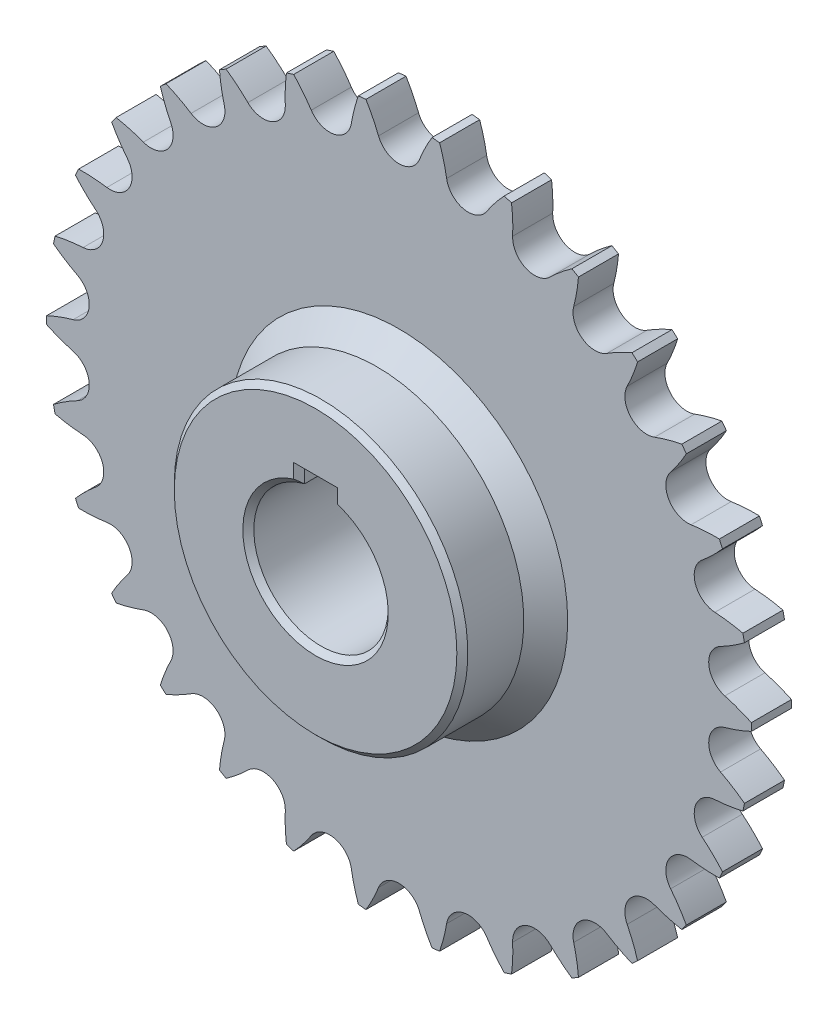
SolidWorks part; units mm, degrees
ref_plane "Front" through (0, 0, 0) normal (0, 0, 1) x (1, 0, 0)
ref_plane "Top" through (0, 0, 0) normal (0, 1, 0) x (1, 0, 0)
ref_plane "Right" through (0, 0, 0) normal (1, 0, 0) x (0, 0, -1)
sketch "Sketch1" plane through (0, 0, 0) normal (0, 0, 1) x (1, 0, 0)
  line L4 (0, -131.4524) -> (0, 131.4524) construction
  line L5 (-131.4524, 0) -> (131.4524, 0) construction
  line L6 (-1.75, -1.75) -> (1.75, 1.75)
  line L7 (-1.75, 1.75) -> (1.75, -1.75)
  circle A174 centre (0, 0) radius 113.558 construction
  circle A175 centre (0, 0) radius 121.498 construction
  arc A176 (117.2084, 19.8216) -> (118.7683, 4.9806) centre (120.9114, 12.7083) ccw
  arc A177 (128.4449, 1.3906) -> (118.7683, 4.9806) centre (102.4723, -53.7809) ccw
  arc A178 (125.9272, 25.345) -> (125.349, 28.0654) centre (0, 0) ccw
  arc A179 (117.2084, 19.8216) -> (125.9272, 25.345) centre (89.0514, 73.9108) ccw
  arc A180 (110.526, 43.7575) -> (115.1374, 29.565) centre (115.627, 37.5695) ccw
  arc A181 (125.349, 28.0654) -> (115.1374, 29.565) centre (111.4147, -31.3004) ccw
  arc A182 (117.9059, 50.9729) -> (116.7747, 53.5136) centre (0, 0) ccw
  arc A183 (110.526, 43.7575) -> (117.9059, 50.9729) centre (71.7385, 90.8105) ccw
  arc A184 (99.0131, 65.7809) -> (106.4745, 52.8574) centre (105.2891, 60.7887) ccw
  arc A185 (116.7747, 53.5136) -> (106.4745, 52.8574) centre (115.4878, -7.452) ccw
  arc A186 (104.7315, 74.373) -> (103.0967, 76.623) centre (0, 0) ccw
  arc A187 (99.0131, 65.7809) -> (104.7315, 74.373) centre (51.2903, 103.7413) ccw
  arc A188 (83.1728, 84.9294) -> (93.1581, 73.8396) centre (90.3496, 81.3512) ccw
  arc A189 (103.0967, 76.623) -> (93.1581, 73.8396) centre (114.5134, 16.7221) ccw
  arc A190 (86.9798, 94.5227) -> (84.913, 96.3836) centre (0, 0) ccw
  arc A191 (83.1728, 84.9294) -> (86.9798, 94.5227) centre (28.6004, 112.1382) ccw
  arc A192 (63.6974, 100.3661) -> (75.7702, 91.5947) centre (71.4614, 98.3582) ccw
  arc A193 (84.913, 96.3836) -> (75.7702, 91.5947) centre (108.5343, 40.1654) ccw
  arc A194 (65.4267, 110.5413) -> (63.0182, 111.9318) centre (0, 0) ccw
  arc A195 (63.6974, 100.3661) -> (65.4267, 110.5413) centre (4.6606, 115.6341) ccw
  arc A196 (41.4382, 111.4163) -> (55.0709, 105.3466) centre (49.45, 111.0665) ccw
  arc A197 (63.0182, 111.9318) -> (55.0709, 105.3466) centre (97.8117, 61.8532) ccw
  arc A198 (41.0142, 121.7286) -> (38.3691, 122.5881) centre (0, 0) ccw
  arc A199 (41.4382, 111.4163) -> (41.0142, 121.7286) centre (-19.4829, 114.0762) ccw
  arc A200 (17.3679, 117.5971) -> (31.9646, 114.4944) centre (25.2774, 118.9206) ccw
  arc A201 (38.3691, 122.5881) -> (31.9646, 114.4944) centre (82.8143, 80.8378) ccw
  arc A202 (14.8091, 127.5959) -> (12.0432, 127.8866) centre (0, 0) ccw
  arc A203 (17.3679, 117.5971) -> (14.8091, 127.5959) centre (-42.775, 107.5326) ccw
  arc A204 (-7.4614, 118.6383) -> (7.4614, 118.6383) centre (0, 121.5774) ccw
  arc A205 (12.0432, 127.8866) -> (7.4614, 118.6383) centre (64.1975, 96.2893) ccw
  arc A206 (-12.0432, 127.8866) -> (-14.8091, 127.5959) centre (0, 0) ccw
  arc A207 (-7.4614, 118.6383) -> (-12.0432, 127.8866) centre (-64.1975, 96.2893) ccw
  arc A208 (-31.9646, 114.4944) -> (-17.3679, 117.5971) centre (-25.2774, 118.9206) ccw
  arc A209 (-14.8091, 127.5959) -> (-17.3679, 117.5971) centre (42.775, 107.5326) ccw
  arc A210 (-38.3691, 122.5881) -> (-41.0142, 121.7286) centre (0, 0) ccw
  arc A211 (-31.9646, 114.4944) -> (-38.3691, 122.5881) centre (-82.8143, 80.8378) ccw
  arc A212 (-55.0709, 105.3466) -> (-41.4382, 111.4163) centre (-49.45, 111.0665) ccw
  arc A213 (-41.0142, 121.7286) -> (-41.4382, 111.4163) centre (19.4829, 114.0762) ccw
  arc A214 (-63.0182, 111.9318) -> (-65.4267, 110.5413) centre (0, 0) ccw
  arc A215 (-55.0709, 105.3466) -> (-63.0182, 111.9318) centre (-97.8117, 61.8532) ccw
  arc A216 (-75.7702, 91.5947) -> (-63.6974, 100.3661) centre (-71.4614, 98.3582) ccw
  arc A217 (-65.4267, 110.5413) -> (-63.6974, 100.3661) centre (-4.6606, 115.6341) ccw
  arc A218 (-84.913, 96.3836) -> (-86.9798, 94.5227) centre (0, 0) ccw
  arc A219 (-75.7702, 91.5947) -> (-84.913, 96.3836) centre (-108.5343, 40.1654) ccw
  arc A220 (-93.1581, 73.8396) -> (-83.1728, 84.9294) centre (-90.3496, 81.3512) ccw
  arc A221 (-86.9798, 94.5227) -> (-83.1728, 84.9294) centre (-28.6004, 112.1382) ccw
  arc A222 (-103.0967, 76.623) -> (-104.7315, 74.373) centre (0, 0) ccw
  arc A223 (-93.1581, 73.8396) -> (-103.0967, 76.623) centre (-114.5134, 16.7221) ccw
  arc A224 (-106.4745, 52.8574) -> (-99.0131, 65.7809) centre (-105.2891, 60.7887) ccw
  arc A225 (-104.7315, 74.373) -> (-99.0131, 65.7809) centre (-51.2903, 103.7413) ccw
  arc A226 (-116.7747, 53.5136) -> (-117.9059, 50.9729) centre (0, 0) ccw
  arc A227 (-106.4745, 52.8574) -> (-116.7747, 53.5136) centre (-115.4878, -7.452) ccw
  arc A228 (-115.1374, 29.565) -> (-110.526, 43.7575) centre (-115.627, 37.5695) ccw
  arc A229 (-117.9059, 50.9729) -> (-110.526, 43.7575) centre (-71.7385, 90.8105) ccw
  arc A230 (-125.349, 28.0654) -> (-125.9272, 25.345) centre (0, 0) ccw
  arc A231 (-115.1374, 29.565) -> (-125.349, 28.0654) centre (-111.4147, -31.3004) ccw
  arc A232 (-118.7683, 4.9806) -> (-117.2084, 19.8216) centre (-120.9114, 12.7083) ccw
  arc A233 (-125.9272, 25.345) -> (-117.2084, 19.8216) centre (-89.0514, 73.9108) ccw
  arc A234 (-128.4449, 1.3906) -> (-128.4449, -1.3906) centre (0, 0) ccw
  arc A235 (-118.7683, 4.9806) -> (-128.4449, 1.3906) centre (-102.4723, -53.7809) ccw
  arc A236 (-117.2084, -19.8216) -> (-118.7683, -4.9806) centre (-120.9114, -12.7083) ccw
  arc A237 (-128.4449, -1.3906) -> (-118.7683, -4.9806) centre (-102.4723, 53.7809) ccw
  arc A238 (-125.9272, -25.345) -> (-125.349, -28.0654) centre (0, 0) ccw
  arc A239 (-117.2084, -19.8216) -> (-125.9272, -25.345) centre (-89.0514, -73.9108) ccw
  arc A240 (-110.526, -43.7575) -> (-115.1374, -29.565) centre (-115.627, -37.5695) ccw
  arc A241 (-125.349, -28.0654) -> (-115.1374, -29.565) centre (-111.4147, 31.3004) ccw
  arc A242 (-117.9059, -50.9729) -> (-116.7747, -53.5136) centre (0, 0) ccw
  arc A243 (-110.526, -43.7575) -> (-117.9059, -50.9729) centre (-71.7385, -90.8105) ccw
  arc A244 (-99.0131, -65.7809) -> (-106.4745, -52.8574) centre (-105.2891, -60.7887) ccw
  arc A245 (-116.7747, -53.5136) -> (-106.4745, -52.8574) centre (-115.4878, 7.452) ccw
  arc A246 (-104.7315, -74.373) -> (-103.0967, -76.623) centre (0, 0) ccw
  arc A247 (-99.0131, -65.7809) -> (-104.7315, -74.373) centre (-51.2903, -103.7413) ccw
  arc A248 (-83.1728, -84.9294) -> (-93.1581, -73.8396) centre (-90.3496, -81.3512) ccw
  arc A249 (-103.0967, -76.623) -> (-93.1581, -73.8396) centre (-114.5134, -16.7221) ccw
  arc A250 (-86.9798, -94.5227) -> (-84.913, -96.3836) centre (0, 0) ccw
  arc A251 (-83.1728, -84.9294) -> (-86.9798, -94.5227) centre (-28.6004, -112.1382) ccw
  arc A252 (-63.6974, -100.3661) -> (-75.7702, -91.5947) centre (-71.4614, -98.3582) ccw
  arc A253 (-84.913, -96.3836) -> (-75.7702, -91.5947) centre (-108.5343, -40.1654) ccw
  arc A254 (-65.4267, -110.5413) -> (-63.0182, -111.9318) centre (0, 0) ccw
  arc A255 (-63.6974, -100.3661) -> (-65.4267, -110.5413) centre (-4.6606, -115.6341) ccw
  arc A256 (-41.4382, -111.4163) -> (-55.0709, -105.3466) centre (-49.45, -111.0665) ccw
  arc A257 (-63.0182, -111.9318) -> (-55.0709, -105.3466) centre (-97.8117, -61.8532) ccw
  arc A258 (-41.0142, -121.7286) -> (-38.3691, -122.5881) centre (0, 0) ccw
  arc A259 (-41.4382, -111.4163) -> (-41.0142, -121.7286) centre (19.4829, -114.0762) ccw
  arc A260 (-17.3679, -117.5971) -> (-31.9646, -114.4944) centre (-25.2774, -118.9206) ccw
  arc A261 (-38.3691, -122.5881) -> (-31.9646, -114.4944) centre (-82.8143, -80.8378) ccw
  arc A262 (-14.8091, -127.5959) -> (-12.0432, -127.8866) centre (0, 0) ccw
  arc A263 (-17.3679, -117.5971) -> (-14.8091, -127.5959) centre (42.775, -107.5326) ccw
  arc A264 (7.4614, -118.6383) -> (-7.4614, -118.6383) centre (0, -121.5774) ccw
  arc A265 (-12.0432, -127.8866) -> (-7.4614, -118.6383) centre (-64.1975, -96.2893) ccw
  arc A266 (12.0432, -127.8866) -> (14.8091, -127.5959) centre (0, 0) ccw
  arc A267 (7.4614, -118.6383) -> (12.0432, -127.8866) centre (64.1975, -96.2893) ccw
  arc A268 (31.9646, -114.4944) -> (17.3679, -117.5971) centre (25.2774, -118.9206) ccw
  arc A269 (14.8091, -127.5959) -> (17.3679, -117.5971) centre (-42.775, -107.5326) ccw
  arc A270 (38.3691, -122.5881) -> (41.0142, -121.7286) centre (0, 0) ccw
  arc A271 (31.9646, -114.4944) -> (38.3691, -122.5881) centre (82.8143, -80.8378) ccw
  arc A272 (55.0709, -105.3466) -> (41.4382, -111.4163) centre (49.45, -111.0665) ccw
  arc A273 (41.0142, -121.7286) -> (41.4382, -111.4163) centre (-19.4829, -114.0762) ccw
  arc A274 (63.0182, -111.9318) -> (65.4267, -110.5413) centre (0, 0) ccw
  arc A275 (55.0709, -105.3466) -> (63.0182, -111.9318) centre (97.8117, -61.8532) ccw
  arc A276 (75.7702, -91.5947) -> (63.6974, -100.3661) centre (71.4614, -98.3582) ccw
  arc A277 (65.4267, -110.5413) -> (63.6974, -100.3661) centre (4.6606, -115.6341) ccw
  arc A278 (84.913, -96.3836) -> (86.9798, -94.5227) centre (0, 0) ccw
  arc A279 (75.7702, -91.5947) -> (84.913, -96.3836) centre (108.5343, -40.1654) ccw
  arc A280 (93.1581, -73.8396) -> (83.1728, -84.9294) centre (90.3496, -81.3512) ccw
  arc A281 (86.9798, -94.5227) -> (83.1728, -84.9294) centre (28.6004, -112.1382) ccw
  arc A282 (103.0967, -76.623) -> (104.7315, -74.373) centre (0, 0) ccw
  arc A283 (93.1581, -73.8396) -> (103.0967, -76.623) centre (114.5134, -16.7221) ccw
  arc A284 (106.4745, -52.8574) -> (99.0131, -65.7809) centre (105.2891, -60.7887) ccw
  arc A285 (104.7315, -74.373) -> (99.0131, -65.7809) centre (51.2903, -103.7413) ccw
  arc A286 (116.7747, -53.5136) -> (117.9059, -50.9729) centre (0, 0) ccw
  arc A287 (106.4745, -52.8574) -> (116.7747, -53.5136) centre (115.4878, 7.452) ccw
  arc A288 (115.1374, -29.565) -> (110.526, -43.7575) centre (115.627, -37.5695) ccw
  arc A289 (117.9059, -50.9729) -> (110.526, -43.7575) centre (71.7385, -90.8105) ccw
  arc A290 (125.349, -28.0654) -> (125.9272, -25.345) centre (0, 0) ccw
  arc A291 (115.1374, -29.565) -> (125.349, -28.0654) centre (111.4147, 31.3004) ccw
  arc A292 (118.7683, -4.9806) -> (117.2084, -19.8216) centre (120.9114, -12.7083) ccw
  arc A293 (125.9272, -25.345) -> (117.2084, -19.8216) centre (89.0514, -73.9108) ccw
  arc A294 (128.4449, -1.3906) -> (128.4449, 1.3906) centre (0, 0) ccw
  arc A295 (118.7683, -4.9806) -> (128.4449, -1.3906) centre (102.4723, 53.7809) ccw
  circle A296 centre (0, 0) radius 24.5
  circle A297 centre (0, 0) radius 1.75
extrude "Boss-Extrude1" add sketch "Sketch1" along normal blind 14.6 contours A292 A295 A294 A177 A176 A179 A178 A181 A180 A183 A182 A185 A184 A187 A186 A189 A188 A191 A190 A193 A192 A195 A194 A197 A196 A199 A198 A201 A200 A203 A202 A205 A204 A207 A206 A209 A208 A211 A210 A213 A212 A215 A214 A217 A216 A219 A218 A221 A220 A223 A222 region at (109.3306, 11.4911, 0)
sketch "Sketch2" plane through (0, 0, 0) normal (0, 0, 1) x (1, 0, 0)
  circle A0 centre (0, 0) radius 53.5
  circle A1 centre (0, 0) radius 24.5
  circle A2 centre (0, 0) radius 24.5 construction
  dimension "D1" = 107
extrude "Boss-Extrude2" add sketch "Sketch2" along normal blind 45
sketch "Sketch4" plane through (0, 0, 45) normal (0, 0, 1) x (1, 0, 0)
  line L1 (-6, 28.5) -> (6, 28.5)
  line L2 (-6, 28.5) -> (-6, 20.5)
  line L7 (-6, 20.5) -> (6, 20.5)
  line L8 (6, 28.5) -> (6, 20.5)
  line L9 (-6, 28.5) -> (6, 20.5) construction
  line L10 (-6, 20.5) -> (6, 28.5) construction
  circle A1 centre (0, 0) radius 24.5 construction
  point P0 (0, 24.5)
  dimension "D1" = 12
  dimension "D2" = 8
extrude "Cut-Extrude1" cut sketch "Sketch4" against normal blind 107.4
chamfer "Chamfer1" distance 2 angle 45 6 edges at (0, -24.5, 45) (53.5, 0, 45) (0, 28.5, 45) (-6, 26.127, 45) (6, 26.127, 45) (0, -24.5, 0)
chamfer "Chamfer2" distance 8 angle 45 1 edges at (53.5, 0, 14.6)
